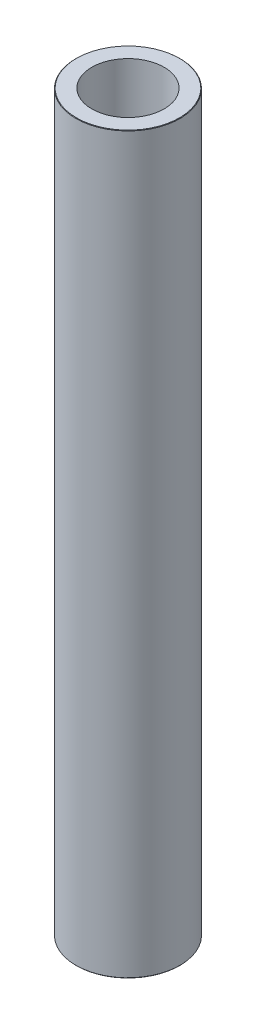
SolidWorks part; units mm, degrees
ref_plane "Front Plane" through (0, 0, 0) normal (0, 0, 1) x (1, 0, 0)
ref_plane "Top Plane" through (0, 0, 0) normal (0, 1, 0) x (1, 0, 0)
ref_plane "Right Plane" through (0, 0, 0) normal (1, 0, 0) x (0, 0, -1)
sketch "Sketch1" plane through (0, 0, 0) normal (0, 1, 0) x (1, 0, 0)
  circle A0 centre (0, 0) radius 42.5
  dimension "SHAFT_OD" = 85
extrude "Boss-Extrude1" add sketch "Sketch1" along normal blind 600
sketch "Sketch2" plane through (0, 0, 0) normal (0, 1, 0) x (1, 0, 0)
  circle A0 centre (0, 0) radius 29.5408
  dimension "BORE_D" = 59.0816
extrude "Cut-Extrude1" cut sketch "Sketch2" along normal through all
chamfer "Chamfer1" distance 0.3222 angle 50.291 2 edges at (0, 600, 42.5) (0, 0, 42.5) first distance on face at (0, 600, 42.5) first distance on face at (0, 0, 29.5408)
